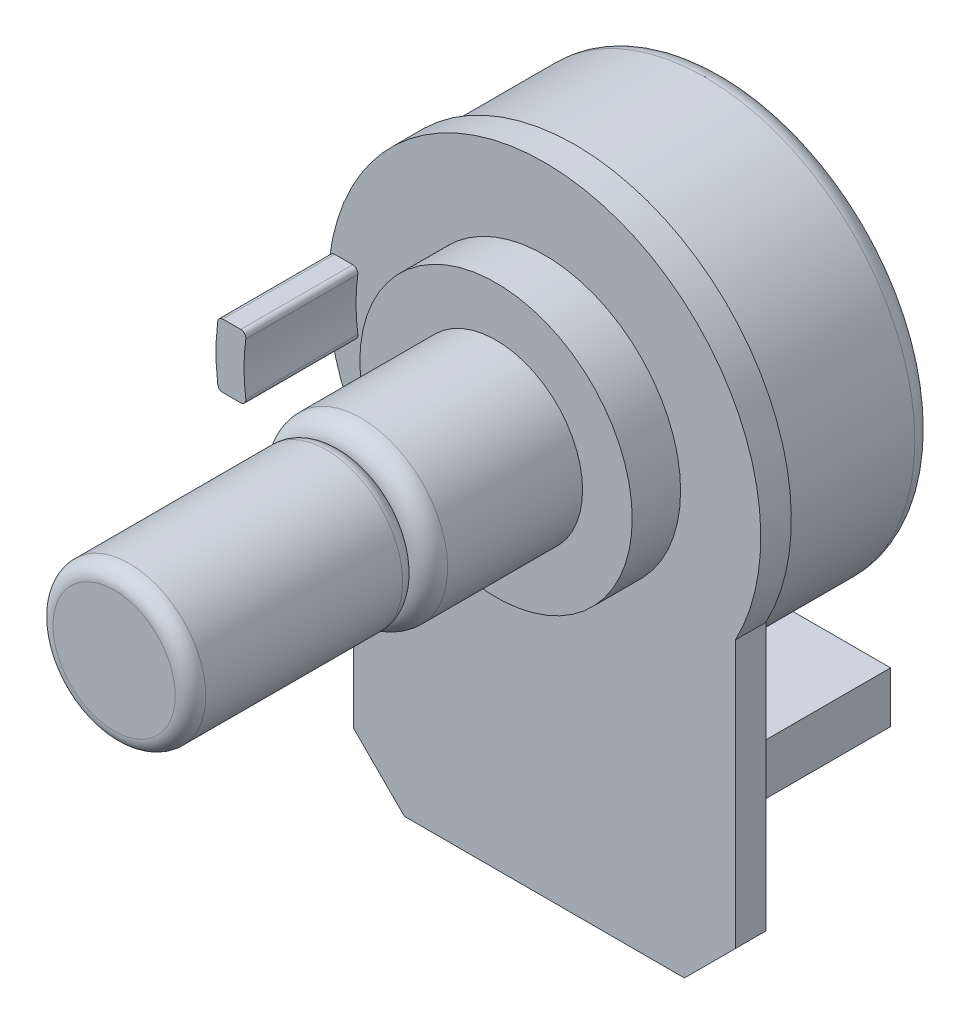
SolidWorks part; units mm, degrees
ref_plane "Front Plane" through (0, 0, 0) normal (0, 0, 1) x (1, 0, 0)
ref_plane "Top Plane" through (0, 0, 0) normal (0, 1, 0) x (1, 0, 0)
ref_plane "Right Plane" through (0, 0, 0) normal (1, 0, 0) x (0, 0, -1)
sketch "Sketch1" plane through (0, 0, 0) normal (0, 0, 1) x (1, 0, 0)
  line L0 (7.5, -4) -> (7.5, -16.5)
  line L1 (7.5, -16.5) -> (-7.5, -16.5)
  line L2 (-7.5, -16.5) -> (-7.5, -4)
  line L3 (0, -16.5) -> (0, 0) construction
  arc A0 (7.5, -4) -> (-7.5, -4) centre (0, 0) ccw
  point P8 (0, 8.5)
  dimension "D1" = 17
  dimension "D2" = 15
  dimension "D3" = 25
extrude "Boss-Extrude1" add sketch "Sketch1" along normal blind 1.2
sketch "Sketch2" plane through (0, 0, 1.2) normal (0, 0, 1) x (1, 0, 0)
  circle A0 centre (0, 0) radius 5.35
  dimension "D1" = 10.7
extrude "Boss-Extrude2" add sketch "Sketch2" along normal blind 1.9
sketch "Sketch3" plane through (0, 0, 3.1) normal (0, 0, 1) x (1, 0, 0)
  circle A0 centre (0, 0) radius 3.4
  dimension "D1" = 6.8
extrude "Boss-Extrude3" add sketch "Sketch3" along normal blind 6.1
fillet "Fillet2" radius 0.8 1 edges at (3.4, 0, 9.2)
sketch "Sketch4" plane through (0, 0, 9.2) normal (0, 0, 1) x (1, 0, 0)
  circle A0 centre (0, 0) radius 3
  dimension "D1" = 6
extrude "Boss-Extrude4" add sketch "Sketch4" along normal offset from surface (8.9 mm away) 15 up to face at (3.4, 0, 3.1) offset beyond the face yes
sketch "Sketch5" plane through (0, 0, 0) normal (0, 0, -1) x (-1, 0, 0)
  circle A0 centre (0, 0) radius 8.25
  dimension "D1" = 16.5
extrude "Boss-Extrude5" add sketch "Sketch5" along normal offset from surface (5.9 mm away) 9 up to face at (3.4, 0, 3.1)
fillet "Fillet1" radius 0.8 1 edges at (8.25, 0, -5.9)
sketch "Sketch6" plane through (0, 0, 0) normal (0, 0, -1) x (-1, 0, 0)
  line L0 (0, -9) -> (0, 0) construction
  line L1 (-6.498, -9) -> (6.498, -9)
  line L2 (-6.498, -9) -> (-6.498, -11)
  line L3 (-6.498, -11) -> (6.498, -11)
  line L4 (6.498, -9) -> (6.498, -11)
  dimension "D1" = 2
  dimension "D2" = 12.996
  dimension "D3" = 9
extrude "Boss-Extrude6" add sketch "Sketch6" along normal up to surface (5.9 mm away) up to face at (7.45, 0, -5.9)
fillet "Fillet3" radius 0.6 2 edges at (3, 0, 9.2) (3, 0, 18.1)
chamfer "Chamfer1" distance 2 angle 45 2 edges at (7.5, -16.5, 0.6) (-7.5, -16.5, 0.6)
sketch "Sketch8" plane through (0, 0, 1.2) normal (0, 0, 1) x (1, 0, 0)
  line L0 (-8.4076, 1.25) -> (-7.2937, 1.25)
  line L1 (-8.4076, -1.25) -> (-7.2937, -1.25)
  line L2 (-7.4, 0) -> (0, 0) construction
  arc A0 (-8.4076, 1.25) -> (-8.4076, -1.25) centre (0, 0) ccw
  arc A1 (7.5, -4) -> (-7.5, -4) centre (0, 0) ccw construction
  arc A2 (-7.2937, 1.25) -> (-7.2937, -1.25) centre (0, 0) ccw
  dimension "D2" = 1.1
  dimension "D1" = 2.5
extrude "Boss-Extrude7" add sketch "Sketch8" along normal offset from surface (4.4 mm away) 2.5 up to face at (3.4, 0, 3.1) offset beyond the face yes
fillet "Fillet4" radius 0.2 4 edges at (-7.2937, 1.25, 3.4) (-8.4076, 1.25, 3.4) (-8.4076, -1.25, 3.4) (-7.2937, -1.25, 3.4)
